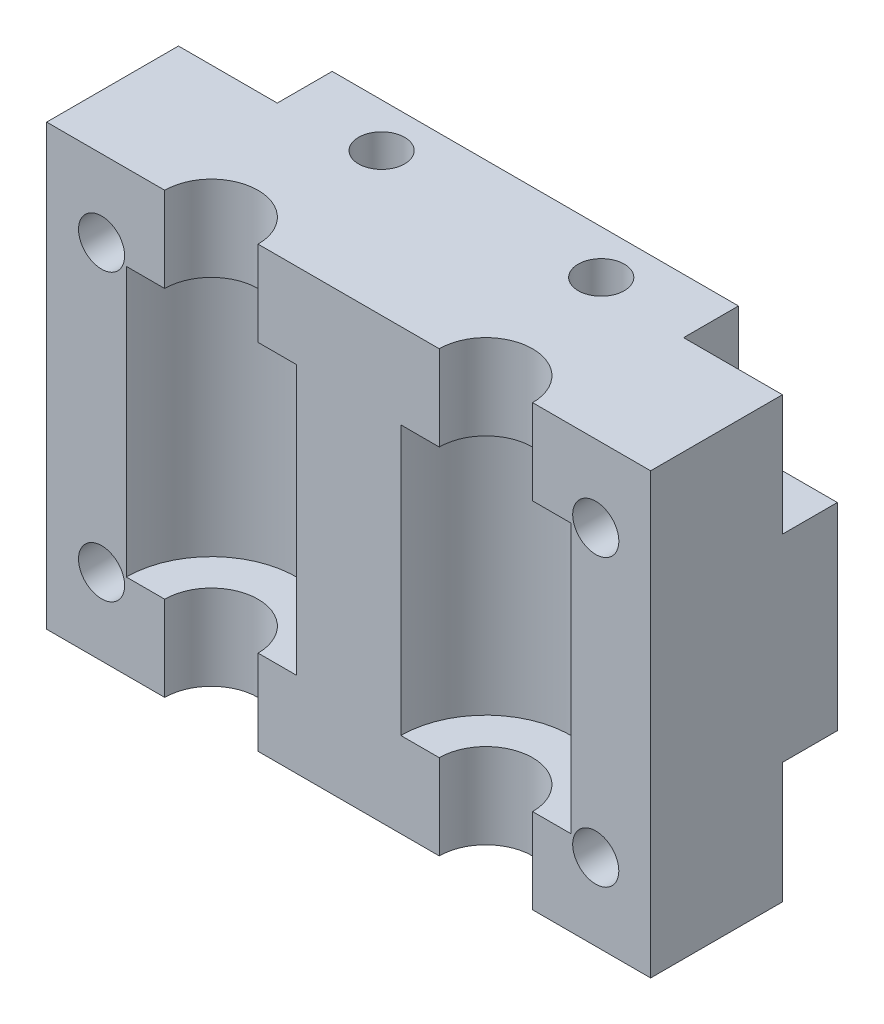
SolidWorks part; units mm, degrees
ref_plane "Plan de face" through (0, 0, 0) normal (0, 0, 1) x (1, 0, 0)
ref_plane "Plan de dessus" through (0, 0, 0) normal (0, 1, 0) x (1, 0, 0)
ref_plane "Plan de droite" through (0, 0, 0) normal (1, 0, 0) x (0, 0, -1)
sketch "Esquisse1" plane through (0, 0, 0) normal (0, 0, 1) x (1, 0, 0)
  line L1 (-27.5, -22.5) -> (27.5, -22.5)
  line L2 (-27.5, -22.5) -> (-27.5, 22.5)
  line L3 (-27.5, 22.5) -> (27.5, 22.5)
  line L4 (27.5, -22.5) -> (27.5, 22.5)
  line L5 (-27.5, -22.5) -> (27.5, 22.5) construction
  line L6 (-27.5, 22.5) -> (27.5, -22.5) construction
  point P0 (0, 0)
  dimension "D1" = 55
  dimension "D2" = 45
extrude "Boss.-Extru.1" add sketch "Esquisse1" along normal blind 12
sketch "Esquisse2" plane through (0, 22.5, 0) normal (0, 1, 0) x (1, 0, 0)
  line L0 (27.5, -12) -> (-27.5, -12) construction
  line L1 (-27.5, -12) -> (-27.5, 0) construction
  line L2 (27.5, -12) -> (27.5, 0) construction
  circle A0 centre (-12.5, -12) radius 4.25
  circle A1 centre (12.5, -12) radius 4.25
  dimension "D1" = 8.5
  dimension "D3" = 8.5
  dimension "D2" = 15
  dimension "D4" = 15
extrude "Enlèv. mat.-Extru.1" cut sketch "Esquisse2" against normal through all
sketch "Esquisse3" plane through (0, 0, 0) normal (0, 1, 0) x (1, 0, 0)
  circle A0 centre (-12.5, -12) radius 7.75
  dimension "D1" = 15.5
extrude "Enlèv. mat.-Extru.2" cut sketch "Esquisse3" against normal blind 12.25 and the other way blind 12.25
sketch "Esquisse9" plane through (0, 0, 12) normal (0, 0, 1) x (1, 0, 0)
  line L0 (-8.25, -22.5) -> (8.25, -22.5) construction
  line L1 (-30.9208, -30.2281) -> (30.1419, -30.2281)
  line L2 (-30.9208, -30.2281) -> (-30.9208, -18)
  line L3 (-30.9208, -18) -> (30.1419, -18)
  line L4 (30.1419, -30.2281) -> (30.1419, -18)
  line L5 (8.25, 22.5) -> (-8.25, 22.5) construction
  line L6 (31.3881, 26.1002) -> (-28.039, 26.1002)
  line L7 (31.3881, 26.1002) -> (31.3881, 18)
  line L8 (31.3881, 18) -> (-28.039, 18)
  line L9 (-28.039, 26.1002) -> (-28.039, 18)
  dimension "D1" = 4.5
  dimension "D2" = 4.5
extrude "Enlèv. mat.-Extru.7" cut sketch "Esquisse9" against normal blind 31
sketch "Sketch1" plane through (0, 0, 0) normal (0, 0, -1) x (-1, 0, 0)
  line L4 (-27.5, -18) -> (27.5, -18)
  line L5 (27.5, -18) -> (27.5, 18)
  line L6 (27.5, 18) -> (-27.5, 18)
  line L7 (-27.5, 18) -> (-27.5, -18)
  line L8 (-27.5, -18) -> (27.5, -18)
  line L9 (27.5, -18) -> (27.5, 18)
  line L10 (27.5, 18) -> (-27.5, 18)
  line L11 (-27.5, 18) -> (-27.5, -18)
  dimension "D1" = 0
extrude "Boss-Extrude1" add sketch "Sketch1" along normal blind 5
sketch "Sketch2" plane through (0, 0, 12) normal (0, 0, 1) x (1, 0, 0)
  line L0 (-27.5, 18) -> (-16.75, 18) construction
  line L1 (-27.5, 18) -> (-27.5, -18) construction
  line L2 (0, 18) -> (0, -18) construction
  line L3 (-8.25, 18) -> (8.25, 18) construction
  line L4 (8.25, -18) -> (-8.25, -18) construction
  line L5 (-27.5, 0) -> (27.5, 0) construction
  line L6 (27.5, -18) -> (27.5, 18) construction
  circle A0 centre (-22.5, 13) radius 2.1
  circle A1 centre (22.5, 13) radius 2.1
  circle A2 centre (22.5, -13) radius 2.1
  circle A3 centre (-22.5, -13) radius 2.1
  dimension "D1" = 4.2
  dimension "D2" = 5
  dimension "D3" = 5
extrude "Cut-Extrude1" cut sketch "Sketch2" against normal through all
sketch "Sketch3" plane through (0, 0, -5) normal (0, 0, -1) x (-1, 0, 0)
  circle A0 centre (-22.5, 13) radius 4
  circle A1 centre (22.5, 13) radius 4
  circle A2 centre (22.5, -13) radius 4
  circle A3 centre (-22.5, -13) radius 4
  dimension "D1" = 8
extrude "Cut-Extrude2" cut sketch "Sketch3" against normal blind 10
sketch "Sketch4" plane through (0, 0, -5) normal (0, 0, -1) x (-1, 0, 0)
  line L0 (-18.5, 13) -> (-18.5, 18)
  line L1 (-22.5, 9) -> (-27.5, 9)
  line L2 (-22.5, -9) -> (-27.5, -9)
  line L3 (-18.5, -13) -> (-18.5, -18)
  line L4 (-27.5, 18) -> (-27.5, -18)
  line L5 (-27.5, -18) -> (27.5, -18)
  line L6 (27.5, -18) -> (27.5, 18)
  line L7 (27.5, 18) -> (-27.5, 18)
  line L8 (-27.5, 18) -> (-27.5, 9)
  line L9 (-27.5, -18) -> (-18.5, -18)
  line L10 (27.5, -18) -> (27.5, -9)
  line L11 (27.5, 18) -> (18.5, 18)
  line L12 (18.5, -13) -> (18.5, -18)
  line L13 (22.5, -9) -> (27.5, -9)
  line L14 (22.5, 9) -> (27.5, 9)
  line L15 (18.5, 13) -> (18.5, 18)
  line L16 (-18.5, 18) -> (-27.5, 18)
  line L17 (-27.5, -9) -> (-27.5, -18)
  line L18 (18.5, -18) -> (27.5, -18)
  line L19 (27.5, 9) -> (27.5, 18)
  circle A0 centre (-22.5, 13) radius 4 construction
  circle A1 centre (-22.5, -13) radius 4 construction
  circle A2 centre (22.5, -13) radius 4 construction
  circle A3 centre (22.5, 13) radius 4 construction
  arc A4 (-18.5, 13) -> (-22.5, 9) centre (-22.5, 13) ccw
  arc A5 (-22.5, -9) -> (-18.5, -13) centre (-22.5, -13) ccw
  arc A6 (18.5, -13) -> (22.5, -9) centre (22.5, -13) ccw
  arc A7 (22.5, 9) -> (18.5, 13) centre (22.5, 13) ccw
  dimension "D1" = 0
extrude "Cut-Extrude3" cut sketch "Sketch4" against normal blind 5
sketch "Sketch5" plane through (0, 18, 0) normal (0, 1, 0) x (1, 0, 0)
  line L0 (-27.5, -12) -> (-27.5, 0) construction
  line L1 (27.5, 0) -> (27.5, 5) construction
  line L2 (-18.5, 5) -> (18.5, 5) construction
  circle A0 centre (-10, 1) radius 2.1
  circle A1 centre (10, 1) radius 2.1
  dimension "D1" = 4.2
  dimension "D2" = 4.2
  dimension "D3" = 17.5
  dimension "D4" = 17.5
  dimension "D5" = 4
  dimension "D6" = 4
extrude "Cut-Extrude4" cut sketch "Sketch5" against normal through all
sketch "Sketch7" plane through (0, 18, 0) normal (0, 1, 0) x (1, 0, 0)
  line L10 (18.5, 5) -> (-18.5, 5)
  line L11 (-18.5, 5) -> (-18.5, 0)
  line L12 (-18.5, 0) -> (-27.5, 0)
  line L13 (-27.5, 0) -> (-27.5, -12)
  line L14 (-27.5, -12) -> (-16.75, -12)
  line L15 (-8.25, -12) -> (8.25, -12)
  line L16 (16.75, -12) -> (27.5, -12)
  line L17 (27.5, -12) -> (27.5, 0)
  line L18 (27.5, 0) -> (18.5, 0)
  line L19 (18.5, 0) -> (18.5, 5)
  line L20 (18.5, 5) -> (-18.5, 5)
  line L21 (-18.5, 5) -> (-18.5, 0)
  line L22 (-18.5, 0) -> (-27.5, 0)
  line L23 (-27.5, 0) -> (-27.5, -12)
  line L24 (-27.5, -12) -> (-16.75, -12)
  line L25 (-8.25, -12) -> (8.25, -12)
  line L26 (16.75, -12) -> (27.5, -12)
  line L27 (27.5, -12) -> (27.5, 0)
  line L28 (27.5, 0) -> (18.5, 0)
  line L29 (18.5, 0) -> (18.5, 5)
  circle A0 centre (10, 1) radius 2.1 construction
  circle A1 centre (-10, 1) radius 2.1 construction
  arc A2 (-8.25, -12) -> (-16.75, -12) centre (-12.5, -12) ccw
  arc A3 (16.75, -12) -> (8.25, -12) centre (12.5, -12) ccw
  arc A4 (-8.25, -12) -> (-16.75, -12) centre (-12.5, -12) ccw
  arc A5 (16.75, -12) -> (8.25, -12) centre (12.5, -12) ccw
  circle A6 centre (10, 1) radius 2.1
  circle A7 centre (-10, 1) radius 2.1
  dimension "D1" = 0
extrude "Boss-Extrude4" add sketch "Sketch7" along normal blind 2
sketch "Sketch8" plane through (0, -18, 0) normal (0, -1, 0) x (1, 0, 0)
  line L10 (-27.5, 0) -> (-18.5, 0)
  line L11 (-18.5, 0) -> (-18.5, -5)
  line L12 (-18.5, -5) -> (18.5, -5)
  line L13 (18.5, -5) -> (18.5, 0)
  line L14 (18.5, 0) -> (27.5, 0)
  line L15 (27.5, 0) -> (27.5, 12)
  line L16 (27.5, 12) -> (16.75, 12)
  line L17 (8.25, 12) -> (-8.25, 12)
  line L18 (-16.75, 12) -> (-27.5, 12)
  line L19 (-27.5, 12) -> (-27.5, 0)
  line L20 (-27.5, 0) -> (-18.5, 0)
  line L21 (-18.5, 0) -> (-18.5, -5)
  line L22 (-18.5, -5) -> (18.5, -5)
  line L23 (18.5, -5) -> (18.5, 0)
  line L24 (18.5, 0) -> (27.5, 0)
  line L25 (27.5, 0) -> (27.5, 12)
  line L26 (27.5, 12) -> (16.75, 12)
  line L27 (8.25, 12) -> (-8.25, 12)
  line L28 (-16.75, 12) -> (-27.5, 12)
  line L29 (-27.5, 12) -> (-27.5, 0)
  circle A0 centre (-10, -1) radius 2.1 construction
  circle A1 centre (10, -1) radius 2.1 construction
  arc A2 (8.25, 12) -> (16.75, 12) centre (12.5, 12) ccw
  arc A3 (-16.75, 12) -> (-8.25, 12) centre (-12.5, 12) ccw
  arc A4 (8.25, 12) -> (16.75, 12) centre (12.5, 12) ccw
  arc A5 (-16.75, 12) -> (-8.25, 12) centre (-12.5, 12) ccw
  circle A6 centre (10, -1) radius 2.1
  circle A7 centre (-10, -1) radius 2.1
  dimension "D1" = 0
extrude "Boss-Extrude5" add sketch "Sketch8" along normal blind 2
sketch "Sketch9" plane through (0, 0, -5) normal (0, 0, -1) x (-1, 0, 0)
  line L0 (-27.5, 20) -> (-27.5, 9) construction
  line L1 (-13.5, 16) -> (-6.5, 16)
  line L2 (-13.5, 16) -> (-13.5, 12.8)
  line L3 (-13.5, 12.8) -> (-6.5, 12.8)
  line L4 (-6.5, 16) -> (-6.5, 12.8)
  line L5 (-18.5, 20) -> (18.5, 20) construction
  line L6 (0, 20) -> (0, -9.1772) construction
  line L7 (13.5, 12.8) -> (6.5, 12.8)
  line L8 (6.5, 16) -> (6.5, 12.8)
  line L9 (13.5, 16) -> (6.5, 16)
  line L10 (13.5, 16) -> (13.5, 12.8)
  line L11 (-27.5, 0) -> (-8.3783, 0) construction
  line L12 (-27.5, 9) -> (-27.5, -9) construction
  line L13 (13.5, -16) -> (13.5, -12.8)
  line L14 (13.5, -16) -> (6.5, -16)
  line L15 (6.5, -16) -> (6.5, -12.8)
  line L16 (13.5, -12.8) -> (6.5, -12.8)
  line L17 (-13.5, -12.8) -> (-6.5, -12.8)
  line L18 (-6.5, -16) -> (-6.5, -12.8)
  line L19 (-13.5, -16) -> (-6.5, -16)
  line L20 (-13.5, -16) -> (-13.5, -12.8)
  point P4 (-10, 16)
  dimension "D1" = 7
  dimension "D2" = 17.5
  dimension "D3" = 4
  dimension "D4" = 3.2
extrude "Cut-Extrude6" cut sketch "Sketch9" against normal blind 8
ref_plane "Plane1" through (0, 0, 0) normal (-1, 0, 0) x (0, 0, 1)
mirror "Mirror1" about plane through (0, 0, 0) normal (-1, 0, 0) of "Enlèv. mat.-Extru.2"
move or copy body "Body-Move/Copy1" [suppressed]
